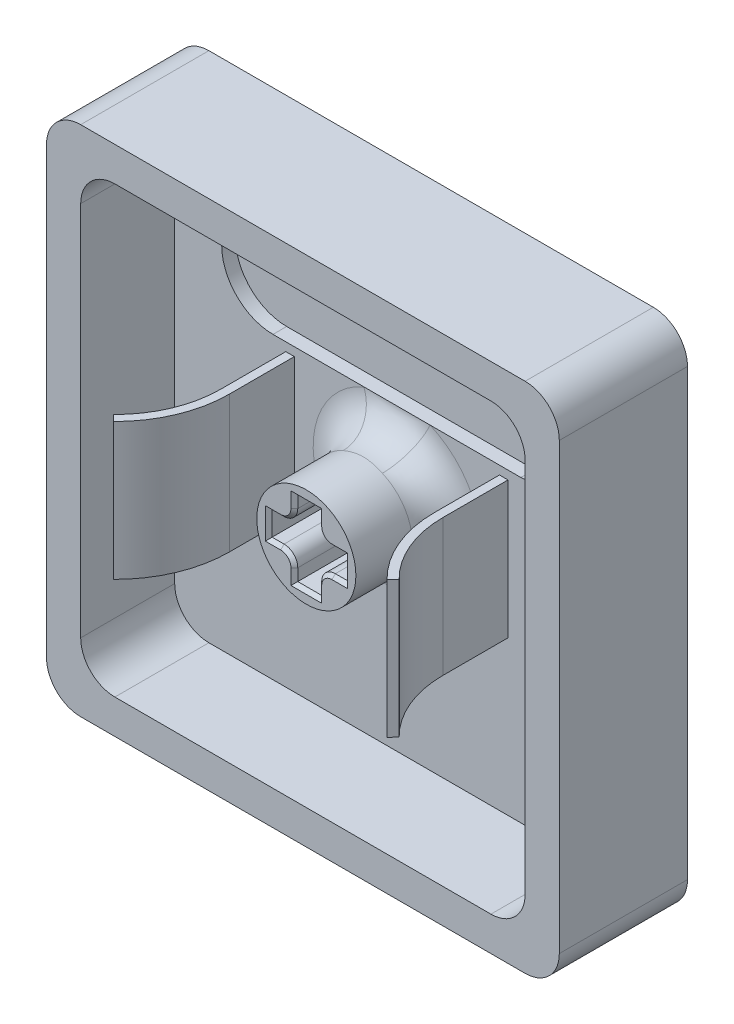
SolidWorks part; units mm, degrees
note: The reader was unsure of these and kept them because the rebuilt part matched: shared geometry of "草图1<6>", "草图1<7>".
other "标注1"
sketch "草图2" plane through (15, -15, 10) normal (0.3933, -0.7926, 0.466) x (0.9059, 0.4207, -0.0491)
ref_plane "前视基准面" through (0, 0, 0) normal (0, 0, 1) x (1, 0, 0)
ref_plane "上视基准面" through (0, 0, 0) normal (0, 1, 0) x (1, 0, 0)
ref_plane "右视基准面" through (0, 0, 0) normal (1, 0, 0) x (0, 0, -1)
sketch "草图1" plane through (0, 0, 0) normal (0, 0, 1) x (1, 0, 0)
  line L0 (-13, 15) -> (13, 15)
  line L1 (-11, 13) -> (11, 13)
  line L2 (-13, 11) -> (-13, -11)
  line L3 (-11, -13) -> (11, -13)
  line L4 (13, 11) -> (13, -11)
  line L5 (0, -13) -> (0, 13) construction
  line L6 (-13, 0) -> (13, 0) construction
  line L7 (15, 13) -> (15, -13)
  line L8 (-13, -15) -> (13, -15)
  line L9 (-15, 13) -> (-15, -13)
  line L10 (-13, -13) -> (13, -13) construction
  line L11 (-2.2, 0.7) -> (2.2, 0.7)
  line L12 (-2.2, 0.7) -> (-2.2, -0.7)
  line L13 (-2.2, -0.7) -> (2.2, -0.7)
  line L14 (2.2, 0.7) -> (2.2, -0.7)
  line L15 (0, -0.7) -> (0, 0.7) construction
  line L16 (-2.2, 0) -> (2.2, 0) construction
  line L17 (-0.7, 2.2) -> (0.7, 2.2)
  line L18 (-0.7, 2.2) -> (-0.7, -2.2)
  line L19 (-0.7, -2.2) -> (0.7, -2.2)
  line L20 (0.7, 2.2) -> (0.7, -2.2)
  line L21 (0, -2.2) -> (0, 2.2) construction
  line L22 (-0.7, 0) -> (0.7, 0) construction
  line L23 (13, 13) -> (13, -13) construction
  line L24 (-13, 13) -> (13, 13) construction
  line L25 (-13, 13) -> (-13, -13) construction
  line L26 (-15, 15) -> (-15, -15) construction
  line L27 (-15, -15) -> (15, -15) construction
  line L28 (15, 15) -> (15, -15) construction
  line L29 (-15, 15) -> (15, 15) construction
  line L36 (-13, 0) -> (-2.5, 0) construction
  circle A0 centre (0, 0) radius 2.9
  arc A1 (11, -13) -> (13, -11) centre (11, -11) ccw
  arc A2 (13, 11) -> (11, 13) centre (11, 11) ccw
  arc A3 (-13, 11) -> (-11, 13) centre (-11, 11) cw
  arc A4 (-13, -11) -> (-11, -13) centre (-11, -11) ccw
  arc A5 (-15, -13) -> (-13, -15) centre (-13, -13) ccw
  arc A6 (13, -15) -> (15, -13) centre (13, -13) ccw
  arc A7 (15, 13) -> (13, 15) centre (13, 13) ccw
  arc A8 (-15, 13) -> (-13, 15) centre (-13, 13) cw
  point P0 (0, 0)
  point P19 (13, -13)
  point P66 (0.0162, 0.0162)
  dimension "D4" = 5.8
  dimension "D9" = 2
  dimension "D1" = 30
  dimension "D2" = 30
  dimension "D5" = 4.4
  dimension "D6" = 1.4
  dimension "D7" = 4.4
  dimension "D8" = 1.4
  dimension "D3" = 2
extrude "凸台-拉伸1" add sketch "草图1" along normal blind 5.5 contours A8 L9 A5 L8 A6 L7 A7 L0 A4 L2 A3 L1 A2 L4 A1 L3
extrude "凸台-拉伸2" add sketch "草图1<6>" along normal blind 5.3 separate body contours A0 L17 L20 L11 L14 L13 L19 L18 L12
sketch "草图1<6>" plane through (0, 0, 0) normal (0, 0, 1) x (1, 0, 0) same geometry as "草图1"
extrude "凸台-拉伸3" add sketch "草图1<7>" against normal blind 2 contours L8 A6 L7 A7 L0 A8 L9 A5
sketch "草图1<7>" plane through (0, 0, 0) normal (0, 0, 1) x (1, 0, 0) same geometry as "草图1"
sketch "草图3" plane through (0, 0, 0) normal (0, 0, 1) x (1, 0, 0)
  line L8 (0.7, 0.7) -> (0.7, 2.2)
  line L10 (0.7, 0.7) -> (0.7, 2.2)
  line L15 (-0.7, 0.7) -> (-2.2, 0.7)
  line L16 (-2.2, 0.7) -> (-2.2, -0.7)
  line L17 (-2.2, -0.7) -> (-0.7, -0.7)
  line L19 (0.7, 2.2) -> (-0.7, 2.2)
  line L20 (0.7, 2.2) -> (-0.7, 2.2)
  line L21 (0.7, -0.7) -> (2.2, -0.7)
  line L22 (2.2, -0.7) -> (2.2, 0.7)
  line L23 (2.2, 0.7) -> (0.7, 0.7)
  line L27 (-0.7, 0.7) -> (-2.2, 0.7)
  line L28 (-2.2, 0.7) -> (-2.2, -0.7)
  line L29 (-2.2, -0.7) -> (-0.7, -0.7)
  line L33 (0.7, -0.7) -> (2.2, -0.7)
  line L34 (2.2, -0.7) -> (2.2, 0.7)
  line L35 (2.2, 0.7) -> (0.7, 0.7)
  line L36 (-0.7, 2.2) -> (-0.7, 0.7)
  line L37 (-0.7, 2.2) -> (-0.7, 0.7)
  line L38 (-0.7, -0.7) -> (-0.7, -2.2)
  line L39 (-0.7, -0.7) -> (-0.7, -2.2)
  line L40 (-0.7, -2.2) -> (0.7, -2.2)
  line L41 (-0.7, -2.2) -> (0.7, -2.2)
  line L42 (0.7, -2.2) -> (0.7, -0.7)
  line L43 (0.7, -2.2) -> (0.7, -0.7)
  dimension "D1" = 0
extrude "凸台-拉伸4" add sketch "草图3" along normal blind 2
sketch "草图5" plane through (0, 0, 0) normal (0, 0, 1) x (1, 0, 0)
  line L6 (7.25, 7.5) -> (-7.25, 7.5) construction
  line L7 (7.25, 4.5) -> (-7.25, 4.5)
  line L9 (7.25, 10.5) -> (-7.25, 10.5)
  line L10 (0, 0) -> (0, -50000) construction
  arc A0 (7.25, 4.5) -> (7.25, 10.5) centre (7.25, 7.5) ccw
  arc A1 (-7.25, 10.5) -> (-7.25, 4.5) centre (-7.25, 7.5) ccw
  point P2 (0, 7.5)
  dimension "D2" = 3
  dimension "D1" = 14.5
  dimension "D3" = 7.5
extrude "切除-拉伸1" cut sketch "草图5" against normal up to next
sketch "草图6" plane through (0, 0, -2) normal (0, 0, -1) x (-1, 0, 0)
  line L10 (7.25, 4.5) -> (-7.25, 4.5) construction
  line L11 (-7.25, 10.5) -> (7.25, 10.5) construction
  line L12 (7.25, 4.5) -> (-7.25, 4.5)
  line L13 (-7.25, 10.5) -> (7.25, 10.5)
  arc A0 (7.25, 4.5) -> (7.25, 10.5) centre (7.25, 7.5) ccw construction
  arc A1 (-7.25, 10.5) -> (-7.25, 4.5) centre (-7.25, 7.5) ccw construction
  arc A2 (7.25, 4.5) -> (7.25, 10.5) centre (7.25, 7.5) ccw
  arc A3 (-7.25, 10.5) -> (-7.25, 4.5) centre (-7.25, 7.5) ccw
extrude "凸台-拉伸6" add sketch "草图6" against normal blind 1.2 separate body
sketch "草图7" plane through (0, 0, 0) normal (0, 0, 1) x (1, 0, 0)
  line L0 (7.25, 4.5) -> (-7.25, 4.5) construction
  line L1 (7.25, 10.5) -> (-7.25, 10.5) construction
  line L2 (7.25, 4.5) -> (-7.25, 4.5)
  line L3 (7.25, 10.5) -> (-7.25, 10.5)
  line L4 (-13, 11) -> (-13, -11)
  line L5 (-11, -13) -> (11, -13)
  line L6 (13, -11) -> (13, 11)
  line L7 (11, 13) -> (-11, 13)
  line L8 (-13, 11) -> (-13, -11)
  line L9 (-11, -13) -> (11, -13)
  line L10 (13, -11) -> (13, 11)
  line L11 (11, 13) -> (-11, 13)
  circle A0 centre (0, 0) radius 2.9 construction
  circle A1 centre (0, 0) radius 2.9
  arc A2 (7.25, 4.5) -> (7.25, 10.5) centre (7.25, 7.5) ccw construction
  arc A3 (-7.25, 10.5) -> (-7.25, 4.5) centre (-7.25, 7.5) ccw construction
  arc A4 (-13, -11) -> (-11, -13) centre (-11, -11) ccw
  arc A5 (11, -13) -> (13, -11) centre (11, -11) ccw
  arc A6 (13, 11) -> (11, 13) centre (11, 11) ccw
  arc A7 (-11, 13) -> (-13, 11) centre (-11, 11) ccw
  arc A8 (-13, -11) -> (-11, -13) centre (-11, -11) ccw
  arc A9 (11, -13) -> (13, -11) centre (11, -11) ccw
  arc A10 (13, 11) -> (11, 13) centre (11, 11) ccw
  arc A11 (-11, 13) -> (-13, 11) centre (-11, 11) ccw
  arc A12 (7.25, 4.5) -> (7.25, 10.5) centre (7.25, 7.5) ccw
  arc A13 (-7.25, 10.5) -> (-7.25, 4.5) centre (-7.25, 7.5) ccw
  dimension "D1" = 0
ref_plane "基准面1" through (0, 0, 0) normal (0, 1, 0) x (1, 0, 0)
sketch "草图9" plane through (0, 0, 0) normal (0, 1, 0) x (1, 0, 0)
  line L0 (-15, 1.1634) -> (15, 1.1634) construction
  line L4 (15, -5.5) -> (13, -5.5)
  line L6 (15, -5.5) -> (13, -5.5) construction
  line L12 (13, -5.5) -> (-13, -5.5)
  line L14 (13, -5.5) -> (-13, -5.5) construction
  line L16 (-13, -5.5) -> (-15, -5.5)
  line L18 (-13, -5.5) -> (-15, -5.5) construction
  line L20 (8, -8.578) -> (8.3505, -8.2214)
  line L21 (6.5, 1.1634) -> (6.5, -3.8069)
  line L22 (6, 1.1634) -> (6, -3.8069)
  line L23 (0, 0) -> (0, 50000) construction
  line L24 (6.5, 1.1634) -> (6, 1.1634)
  line L25 (-6, 1.1634) -> (-6, -3.8069)
  line L26 (-6.5, 1.1634) -> (-6, 1.1634)
  line L27 (-6.5, 1.1634) -> (-6.5, -3.8069)
  line L28 (-8, -8.578) -> (-8.3505, -8.2214)
  line L29 (-15, -5.5) -> (-15, 2)
  line L30 (-15, -5.5) -> (-15, 2) construction
  line L31 (-15, 2) -> (-13, 2)
  line L32 (-15, 2) -> (-13, 2) construction
  line L33 (-13, 2) -> (13, 2)
  line L34 (-13, 2) -> (13, 2) construction
  line L35 (13, 2) -> (15, 2)
  line L36 (13, 2) -> (15, 2) construction
  line L37 (15, 2) -> (15, -5.5)
  line L38 (15, 2) -> (15, -5.5) construction
  arc A0 (6.5, -3.8069) -> (8.3505, -8.2214) centre (12.6909, -3.8069) ccw
  arc A1 (6, -3.8069) -> (8, -8.578) centre (12.6909, -3.8069) ccw
  arc A2 (-6.5, -3.8069) -> (-8.3505, -8.2214) centre (-12.6909, -3.8069) cw
  arc A3 (-6, -3.8069) -> (-8, -8.578) centre (-12.6909, -3.8069) cw
  point P1 (0, 0)
  point P3 (15, -1.75)
  point P4 (-4.5677, -1.75)
  point P5 (5.0614, -3.9811)
  point P6 (-7.1873, -9.1234)
  point P31 (-5.1941, -3.7913)
  point P32 (-6.0337, -3.8198)
  point P33 (-7.2536, -9.0361)
  point P34 (-5.3416, -3.8069)
  point P35 (15, -1.75)
  point P40 (0, 0)
  point P41 (0, 1.1634)
  dimension "D1" = 0.5
  dimension "D2" = 0.5
  dimension "D3" = 2
  dimension "D4" = 12
extrude "凸台-拉伸9" add sketch "草图9" along normal mid plane 8 separate body
fillet "圆角4" radius 0.8 4 edges at (-0.7, 0.7, 3.65) (0.7, 0.7, 3.65) (-0.7, -0.7, 3.65) (0.7, -0.7, 3.65)
chamfer "倒角1" distance 0.2 angle 45 16 edges at (-0.7, 1.85, 5.3) (-1.85, 0.7, 5.3) (-2.2, 0, 5.3) (-1.85, -0.7, 5.3) (-0.7, -1.85, 5.3) (0, -2.2, 5.3) (0.7, -1.85, 5.3) (1.85, -0.7, 5.3) (2.2, 0, 5.3) (1.85, 0.7, 5.3) (0.7, 1.85, 5.3) (0, 2.2, 5.3) (-0.9343, -0.9343, 5.3) (0.9343, -0.9343, 5.3) (0.9343, 0.9343, 5.3) (-0.9343, 0.9343, 5.3)
fillet "圆角5" radius 2 1 edges at (2.9, 0, 0)
